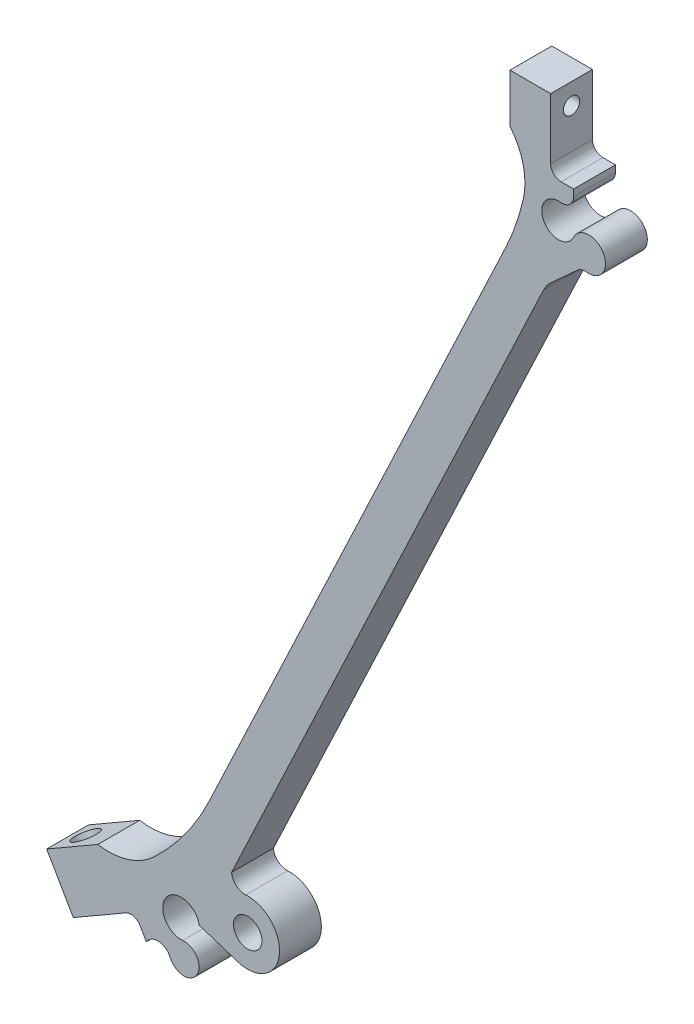
SolidWorks part; units mm, degrees
material "6061-T6 (SS)"
ref_plane "Front Plane" through (0, 0, 0) normal (0, 0, 1) x (1, 0, 0)
ref_plane "Top Plane" through (0, 0, 0) normal (0, 1, 0) x (1, 0, 0)
ref_plane "Right Plane" through (0, 0, 0) normal (1, 0, 0) x (0, 0, -1)
sketch "Sketch1" plane through (0, 0, 0) normal (0, 0, 1) x (1, 0, 0)
  line L0 (0, 0) -> (183.642, 142.5448) construction
  line L1 (0, 0) -> (183.642, 0) construction
  line L2 (0, 0) -> (0, 142.5448) construction
  line L3 (0, 142.5448) -> (183.642, 142.5448) construction
  line L4 (183.642, 0) -> (183.642, 142.5448) construction
  line L5 (91.821, 187.5086) -> (91.821, 71.2724) construction
  line L6 (91.821, 71.2724) -> (192.4845, 13.1543) construction
  line L7 (91.821, 71.2724) -> (-8.8425, 13.1543) construction
  line L8 (17.6741, 34.5985) -> (23.7376, 24.0962) construction
  line L9 (15.8347, 31.4345) -> (25.1835, 36.832)
  line L10 (25.1835, 36.832) -> (26.9297, 33.8074)
  line L11 (26.9297, 33.8074) -> (37.9282, 40.1574) construction
  line L12 (40.3017, 50.3021) -> (87.2277, 149.6422)
  line L13 (91.821, 152.5524) -> (91.821, 165.2524) construction
  line L14 (91.821, 165.2524) -> (88.3285, 165.2524)
  line L15 (97.0619, 172.8724) -> (88.3285, 172.8724) construction
  line L16 (88.3285, 165.2524) -> (88.3285, 176.0474)
  line L17 (88.3285, 176.0474) -> (85.1535, 176.0474)
  line L18 (85.1535, 176.0474) -> (85.1535, 160.1182)
  line L19 (85.1535, 160.1182) -> (31.3755, 46.2729)
  line L20 (31.3755, 46.2729) -> (13.2947, 35.8339)
  line L21 (13.2947, 35.8339) -> (15.8347, 31.4345)
  line L22 (91.821, 165.2524) -> (91.821, 164.2635)
  line L23 (91.821, 153.5413) -> (91.821, 152.5524) construction
  line L24 (26.9297, 33.8074) -> (27.7861, 34.3018)
  line L25 (37.9282, 40.1574) -> (37.0719, 39.663) construction
  line L26 (32.2093, 39.5129) -> (32.6487, 34.4519) construction
  line L27 (89.5197, 159.9774) -> (94.1223, 157.8274) construction
  line L28 (35.6392, 39.5099) -> (40.7743, 37.8607)
  line L29 (92.4048, 154.8585) -> (88.409, 151.236)
  circle A0 centre (91.821, 71.2724) radius 116.2362 construction
  arc A1 (37.7343, 44.8672) -> (37.9282, 40.1574) centre (42.3276, 42.6974) ccw construction
  arc A2 (91.821, 152.5524) -> (87.2277, 149.6422) centre (91.821, 147.4724) ccw construction
  arc A3 (89.8275, 162.4987) -> (91.821, 158.9024) centre (89.5197, 159.9774) ccw
  arc A4 (93.8145, 155.3061) -> (91.821, 158.9024) centre (94.1223, 157.8274) ccw
  arc A5 (93.8145, 155.3061) -> (91.821, 153.5413) centre (93.599, 153.5413) ccw construction
  arc A6 (91.821, 164.2635) -> (89.8275, 162.4987) centre (90.043, 164.2635) cw
  arc A7 (30.3113, 33.4579) -> (32.429, 36.9824) centre (32.6487, 34.4519) ccw
  arc A8 (34.5467, 40.5069) -> (32.429, 36.9824) centre (32.2093, 39.5129) ccw
  arc A9 (37.0719, 39.663) -> (34.5467, 40.5069) centre (36.1829, 41.2028) cw construction
  arc A10 (27.7861, 34.3018) -> (30.3113, 33.4579) centre (28.6751, 32.762) cw
  arc A11 (40.7743, 37.8607) -> (42.0178, 47.7679) centre (42.3276, 42.6974) ccw
  circle A12 centre (42.3276, 42.6974) radius 2.159
  arc A13 (40.3017, 50.3021) -> (42.0178, 47.7679) centre (41.9093, 49.5426) ccw
  arc A14 (34.5467, 40.5069) -> (35.6392, 39.5099) centre (36.1829, 41.2028) ccw
  arc A15 (87.2277, 149.6422) -> (88.409, 151.236) centre (91.821, 147.4724) cw
  arc A16 (93.8145, 155.3061) -> (92.4048, 154.8585) centre (93.599, 153.5413) ccw
  point P11 (0, 0)
  point P37 (0, 0)
  point P40 (91.821, 162.7124)
  point P48 (0, 0)
  point P51 (29.1294, 35.0774)
  point P53 (32.429, 36.9824)
  point P54 (91.821, 158.9024)
  point P58 (0, 0)
  point P63 (0, 0)
  point P65 (0, 0)
  point P66 (0, 0)
  point P67 (0, 0)
  point P68 (0, 0)
  dimension "D18" = 5.08
  dimension "D20" = 1.778
  dimension "D22" = 1.778
  dimension "D23" = 5.08
  dimension "D24" = 3.302
  dimension "D25" = 3.302
  dimension "D26" = 4.318
  dimension "D27" = 1.778
  dimension "D1" = 183.642
  dimension "D2" = 142.5448
  dimension "D3" = 120
  dimension "D4" = 120
  dimension "D5" = 82.55
  dimension "D6" = 3.175
  dimension "D7" = 6.35
  dimension "D8" = 12.7
  dimension "D9" = 7.62
  dimension "D10" = 3.175
  dimension "D11" = 5.08
  dimension "D12" = 6.985
  dimension "D13" = 6.985
  dimension "D14" = 12.7
  dimension "D15" = 101.6
  dimension "D16" = 7.62
  dimension "D17" = 3.175
  dimension "D19" = 2.54
  dimension "D21" = 2.54
extrude "Boss-Extrude1" add sketch "Sketch1" along normal blind 6.35
sketch "Sketch2" plane through (-9.6529, 16.7192, 0) normal (0.5, -0.866, 0) x (-0.866, -0.5, 0)
  line L0 (-29.4305, -6.35) -> (-29.4305, 0) construction
  circle A0 centre (-32.6055, -3.175) radius 1.8288
  point P2 (-29.4305, -3.175)
  dimension "D1" = 3.6576
  dimension "D2" = 3.175
extrude "Cut-Extrude1" cut sketch "Sketch2" against normal through all
sketch "Sketch3" plane through (88.3285, 0, 0) normal (1, 0, 0) x (0, 0, -1)
  line L0 (-6.35, 176.0474) -> (0, 176.0474) construction
  circle A0 centre (-3.175, 172.8724) radius 0.635
  point P2 (-3.175, 176.0474)
  dimension "D1" = 1.27
  dimension "D2" = 3.175
extrude "Cut-Extrude2" cut sketch "Sketch3" against normal through all
fillet "Fillet1" radius 1.5875 2 edges at (25.1835, 36.832, 3.175) (88.3285, 165.2524, 3.175)
fillet "Fillet2" radius 38.1 2 edges at (85.1535, 160.1182, 3.175) (31.3755, 46.2729, 3.175)
hole_wizard "M3x0.5 Tapped Hole1" positions "Sketch5" profile "Sketch4" tap size "M3x0.5" standard "ANSI Metric"
sketch "Sketch5" plane through (85.1535, 0, 0) normal (-1, 0, 0) x (0, 0, 1)
  point P0 (3.175, 172.8724)
sketch "Sketch4" plane through (85.1535, 172.8724, 3.175) normal (0, 1, 0) x (0, 0, 1)
  line L0 (0, 0) -> (0, 8.2517)
  line L1 (0, 8.2517) -> (1.25, 7.5006)
  line L2 (1.25, 7.5006) -> (1.25, 0)
  line L5 (1.25, 0) -> (0, 0)
  line L10 (0, 8.2517) -> (-1.25, 7.5006) construction
  line L11 (0, -6.35) -> (0, 107.95) construction
  dimension "Tap Drill Dia." = 2.5
  dimension "Tap Drill Depth" = 7.5006
  dimension "Drill Angle" = 118
cosmetic thread "Hole Thread2" parameters "D1"=5.08, "D2"=3
sketch "Croquis1" plane through (0, 0, 0) normal (0, 0, -1) x (-1, 0, 0)
  line L0 (-42.3493, 37.6174) -> (-34.8501, 40.0259)
  line L1 (-40.8507, 38.0987) -> (-35.7156, 39.748) construction
  line L2 (-32.4506, 36.7333) -> (-32.429, 36.9824)
  line L14 (-15.8347, 31.4345) -> (-13.2947, 35.8339)
  line L15 (-13.2947, 35.8339) -> (-21.0622, 40.3185)
  line L16 (-36.462, 57.0407) -> (-81.5033, 152.3909)
  line L17 (-85.1535, 168.6642) -> (-85.1535, 176.0474)
  line L18 (-85.1535, 176.0474) -> (-88.3285, 176.0474)
  line L19 (-88.3285, 176.0474) -> (-88.3285, 166.8399)
  line L20 (-89.916, 165.2524) -> (-91.821, 165.2524)
  line L21 (-91.821, 165.2524) -> (-91.821, 164.2635)
  line L22 (-92.4048, 154.8585) -> (-88.409, 151.236)
  line L23 (-87.2277, 149.6422) -> (-40.3017, 50.3021)
  line L24 (-40.7743, 37.8607) -> (-35.6392, 39.5099)
  line L25 (-27.7861, 34.3018) -> (-26.9297, 33.8074)
  line L26 (-26.9297, 33.8074) -> (-25.9772, 35.4572)
  line L27 (-23.8087, 36.0382) -> (-15.8347, 31.4345)
  line L28 (-15.8347, 31.4345) -> (-13.2947, 35.8339)
  line L29 (-13.2947, 35.8339) -> (-21.0622, 40.3185)
  line L30 (-36.462, 57.0407) -> (-81.5033, 152.3909)
  line L31 (-85.1535, 168.6642) -> (-85.1535, 176.0474)
  line L32 (-85.1535, 176.0474) -> (-88.3285, 176.0474)
  line L33 (-88.3285, 176.0474) -> (-88.3285, 166.8399)
  line L34 (-89.916, 165.2524) -> (-91.821, 165.2524)
  line L35 (-91.821, 165.2524) -> (-91.821, 164.2635)
  line L36 (-92.4048, 154.8585) -> (-88.409, 151.236)
  line L37 (-87.2277, 149.6422) -> (-39.885, 49.4201)
  line L38 (-40.7743, 37.8607) -> (-35.6392, 39.5099)
  line L39 (-27.7861, 34.3018) -> (-26.9297, 33.8074)
  line L40 (-26.9297, 33.8074) -> (-25.9772, 35.4572)
  line L41 (-23.8087, 36.0382) -> (-15.8347, 31.4345)
  arc A0 (-32.4506, 36.7333) -> (-30.5413, 33.5557) centre (-32.6487, 34.4519) ccw
  arc A1 (-26.9334, 33.801) -> (-30.5413, 33.5557) centre (-28.6751, 32.762) ccw
  arc A2 (-42.033, 47.5184) -> (-39.885, 49.4201) centre (-41.9093, 49.5426) ccw
  arc A3 (-42.033, 47.5184) -> (-40.8507, 38.0987) centre (-42.3276, 42.6974) ccw
  arc A4 (-42.033, 47.5184) -> (-40.0756, 50.4088) centre (-41.9093, 49.5426) ccw construction
  arc A5 (-27.6611, 34.5183) -> (-30.5413, 33.5557) centre (-28.6751, 32.762) ccw construction
  arc A6 (-32.4506, 36.7333) -> (-34.958, 39.9913) centre (-32.2093, 39.5129) ccw
  arc A7 (-32.4506, 36.7333) -> (-34.7767, 40.6048) centre (-32.2093, 39.5129) ccw construction
  arc A15 (-36.462, 57.0407) -> (-21.0622, 40.3185) centre (-2.0122, 73.314) ccw
  arc A16 (-85.1535, 168.6642) -> (-81.5033, 152.3909) centre (-47.0535, 168.6642) ccw
  arc A17 (-89.916, 165.2524) -> (-88.3285, 166.8399) centre (-89.916, 166.8399) ccw
  arc A18 (-91.821, 164.2635) -> (-89.8275, 162.4987) centre (-90.043, 164.2635) ccw
  arc A19 (-91.821, 158.9024) -> (-89.8275, 162.4987) centre (-89.5197, 159.9774) ccw
  arc A20 (-91.821, 158.9024) -> (-93.8145, 155.3061) centre (-94.1223, 157.8274) ccw
  arc A21 (-92.4048, 154.8585) -> (-93.8145, 155.3061) centre (-93.599, 153.5413) ccw
  arc A22 (-87.2277, 149.6422) -> (-88.409, 151.236) centre (-91.821, 147.4724) ccw
  arc A23 (-42.0178, 47.7679) -> (-40.3017, 50.3021) centre (-41.9093, 49.5426) ccw
  arc A24 (-42.0178, 47.7679) -> (-40.7743, 37.8607) centre (-42.3276, 42.6974) ccw
  arc A25 (-35.6392, 39.5099) -> (-34.5467, 40.5069) centre (-36.1829, 41.2028) ccw
  arc A26 (-32.429, 36.9824) -> (-34.5467, 40.5069) centre (-32.2093, 39.5129) ccw
  arc A27 (-32.429, 36.9824) -> (-30.3113, 33.4579) centre (-32.6487, 34.4519) ccw
  arc A28 (-27.7861, 34.3018) -> (-30.3113, 33.4579) centre (-28.6751, 32.762) ccw
  arc A29 (-23.8087, 36.0382) -> (-25.9772, 35.4572) centre (-24.6024, 34.6634) ccw
  arc A30 (-36.462, 57.0407) -> (-21.0622, 40.3185) centre (-2.0122, 73.314) ccw
  arc A31 (-85.1535, 168.6642) -> (-81.5033, 152.3909) centre (-47.0535, 168.6642) ccw
  arc A32 (-89.916, 165.2524) -> (-88.3285, 166.8399) centre (-89.916, 166.8399) ccw
  arc A33 (-91.821, 164.2635) -> (-89.8275, 162.4987) centre (-90.043, 164.2635) ccw
  arc A34 (-91.821, 158.9024) -> (-89.8275, 162.4987) centre (-89.5197, 159.9774) ccw
  arc A35 (-91.821, 158.9024) -> (-93.8145, 155.3061) centre (-94.1223, 157.8274) ccw
  arc A36 (-92.4048, 154.8585) -> (-93.8145, 155.3061) centre (-93.599, 153.5413) ccw
  arc A37 (-87.2277, 149.6422) -> (-88.409, 151.236) centre (-91.821, 147.4724) ccw
  arc A38 (-42.0178, 47.7679) -> (-40.3017, 50.3021) centre (-41.9093, 49.5426) ccw
  arc A39 (-42.0178, 47.7679) -> (-40.7743, 37.8607) centre (-42.3276, 42.6974) ccw
  arc A40 (-35.6392, 39.5099) -> (-34.5467, 40.5069) centre (-36.1829, 41.2028) ccw
  arc A41 (-32.429, 36.9824) -> (-34.5467, 40.5069) centre (-32.2093, 39.5129) ccw
  arc A43 (-27.7861, 34.3018) -> (-30.3113, 33.4579) centre (-28.6751, 32.762) ccw
  arc A44 (-23.8087, 36.0382) -> (-25.9772, 35.4572) centre (-24.6024, 34.6634) ccw
  arc A51 (-32.429, 36.9824) -> (-30.3113, 33.4579) centre (-32.6487, 34.4519) ccw construction
  dimension "D1" = 0
  dimension "D2" = 0.25
  dimension "D3" = 0.25
  dimension "D4" = 0.25
  dimension "D6" = 0.25
extrude "Cortar-Extruir1" cut sketch "Croquis1" against normal blind 10
sketch "Croquis7" plane through (85.1535, 0, 0) normal (-1, 0, 0) x (0, 0, 1)
  line L4 (0, 176.0474) -> (0, 168.6642)
  line L5 (0, 168.6642) -> (6.35, 168.6642)
  line L6 (6.35, 168.6642) -> (6.35, 176.0474)
  line L7 (6.35, 176.0474) -> (0, 176.0474)
  line L8 (0, 176.0474) -> (0, 168.6642)
  line L9 (0, 168.6642) -> (6.35, 168.6642)
  line L10 (6.35, 168.6642) -> (6.35, 176.0474)
  line L11 (6.35, 176.0474) -> (0, 176.0474)
  circle A0 centre (3.175, 172.8724) radius 1.25 construction
  circle A1 centre (3.175, 172.8724) radius 1.25
  dimension "D1" = 0
sketch "Croquis8" plane through (-12.1929, 21.1186, 0) normal (-0.5, 0.866, 0) x (0.866, 0.5, 0)
  line L4 (29.4305, -6.35) -> (38.3996, -6.35)
  line L5 (38.3996, -6.35) -> (38.3996, 0)
  line L6 (38.3996, 0) -> (29.4305, 0)
  line L7 (29.4305, 0) -> (29.4305, -6.35)
  line L8 (29.4305, -6.35) -> (38.3996, -6.35)
  line L9 (38.3996, -6.35) -> (38.3996, 0)
  line L10 (38.3996, 0) -> (29.4305, 0)
  line L11 (29.4305, 0) -> (29.4305, -6.35)
  circle A0 centre (32.6055, -3.175) radius 1.8288 construction
  circle A1 centre (32.6055, -3.175) radius 1.8288
  dimension "D1" = 0
extrude "Saliente-Extruir3" add sketch "Croquis8" along normal blind 3
extrude "Saliente-Extruir4" add sketch "Croquis7" along normal blind 3
fillet "Redondeo1" radius 10 2 edges at (21.0622, 40.3185, 3.175) (85.1535, 168.6642, 3.175)
